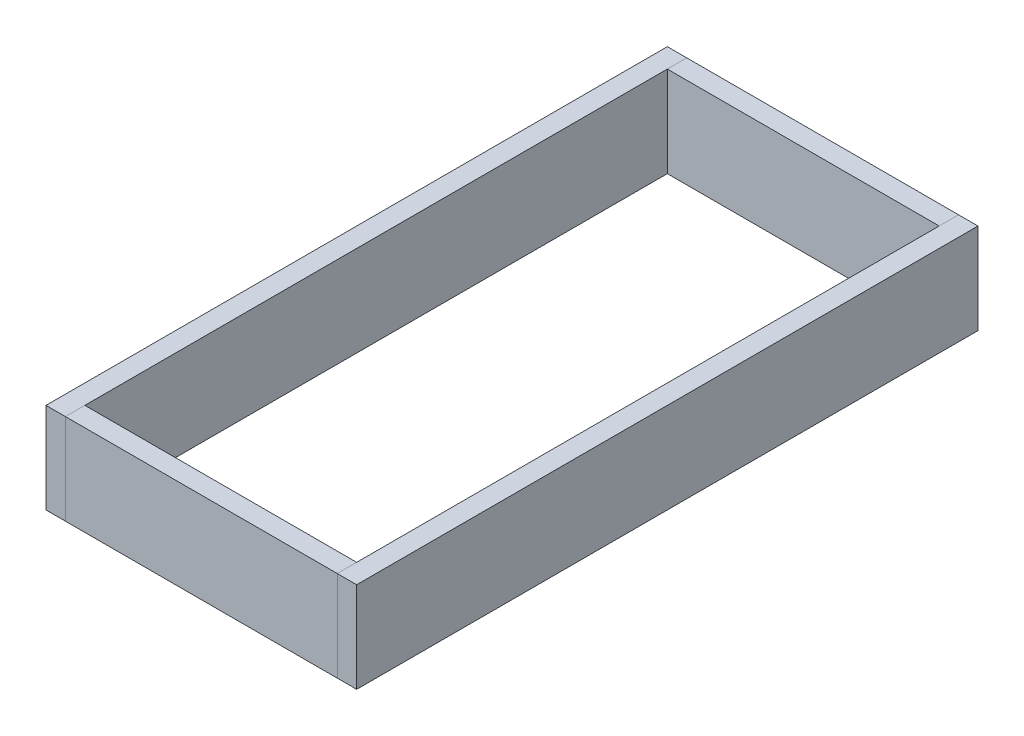
SolidWorks part; units mm, degrees
ref_plane "Front Plane" through (0, 0, 0) normal (0, 0, 1) x (1, 0, 0)
ref_plane "Top Plane" through (0, 0, 0) normal (0, 1, 0) x (1, 0, 0)
ref_plane "Right Plane" through (0, 0, 0) normal (1, 0, 0) x (0, 0, -1)
sketch "Sketch1" plane through (0, 0, 0) normal (0, 1, 0) x (1, 0, 0)
  line L0 (-152.4, -304.8) -> (152.4, 304.8) construction
  line L1 (-152.4, 304.8) -> (152.4, 304.8)
  line L2 (-152.4, 304.8) -> (-152.4, -304.8)
  line L3 (-152.4, -304.8) -> (152.4, -304.8)
  line L4 (152.4, 304.8) -> (152.4, -304.8)
  line L5 (0, 0) -> (0, 232.3863) construction
  line L6 (0, 0) -> (300.98, 0) construction
  line L7 (-133.35, 304.8) -> (-133.35, -304.8)
  line L8 (133.35, 304.8) -> (133.35, -304.8)
  line L9 (-133.35, -285.75) -> (133.35, -285.75)
  line L10 (-133.35, 285.75) -> (133.35, 285.75)
  point P4 (0, 0)
  point P18 (0, 0)
  dimension "D1" = 609.6
  dimension "D2" = 304.8
  dimension "D3" = 19.05
  dimension "D4" = 19.05
extrude "Boss-Extrude1" add sketch "Sketch1" along normal blind 88.9 contours L7 L1 L2 L3 | L1 L8 L3 L4 region at (-142.875, 0, 0) region at (142.875, 0, 0)
extrude "Boss-Extrude2" add sketch "Sketch1<5>" along normal blind 88.9 separate body contours L9 L7 L3 L8 | L7 L10 L8 L1 region at (0, 0, -295.275) region at (0, 0, 295.275)
sketch "Sketch1<5>" plane through (0, 0, 0) normal (0, 1, 0) x (1, 0, 0) same geometry as "Sketch1"
